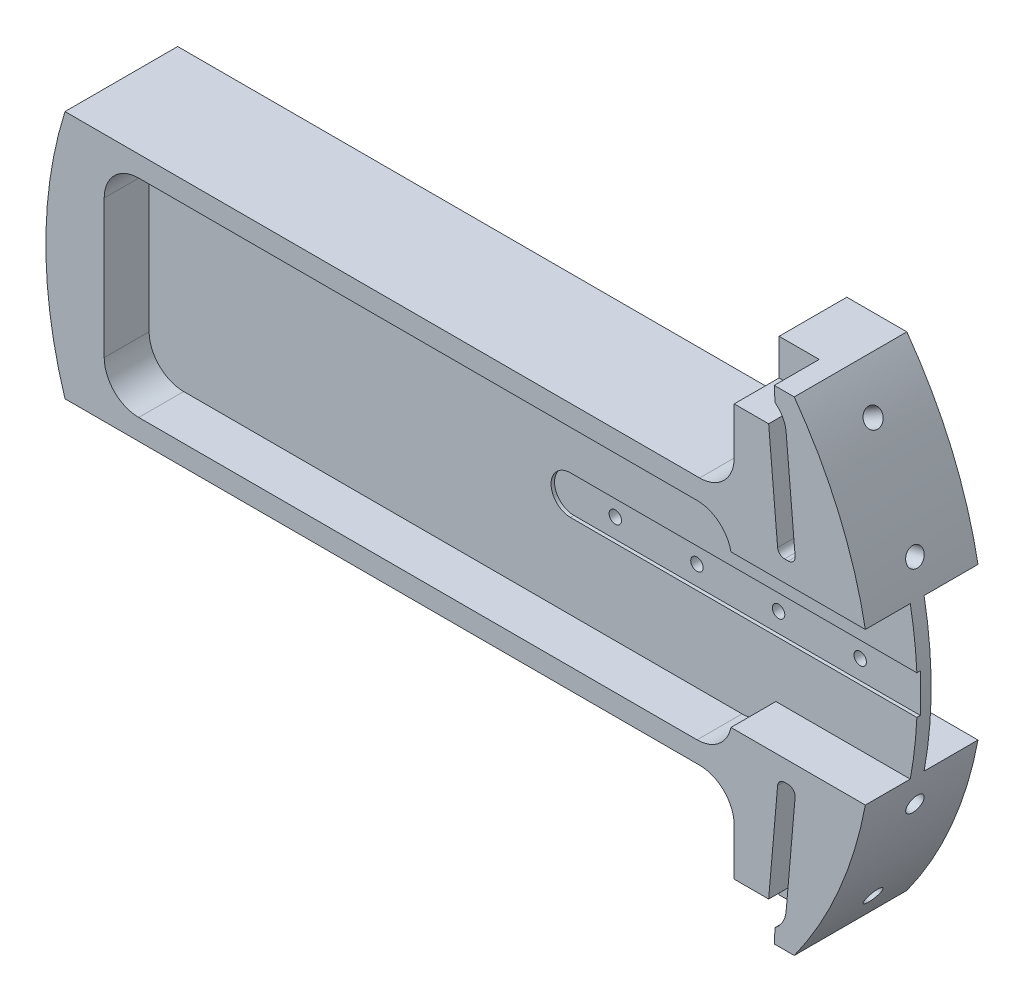
SolidWorks part; units mm, degrees
ref_plane "Front Plane" through (0, 0, 0) normal (0, 0, 1) x (1, 0, 0)
ref_plane "Top Plane" through (0, 0, 0) normal (0, 1, 0) x (1, 0, 0)
ref_plane "Right Plane" through (0, 0, 0) normal (1, 0, 0) x (0, 0, -1)
sketch "Sketch1" plane through (0, 0, 0) normal (0, 0, 1) x (1, 0, 0)
  line L0 (0, 0) -> (91.8237, 0) construction
  line L2 (-71.5726, 25.4) -> (-65.2226, 25.4)
  line L3 (50.546, 44.45) -> (50.546, 22.86)
  line L4 (50.546, -44.45) -> (50.546, -22.86)
  line L5 (44.196, -16.51) -> (-58.8726, -16.51)
  line L6 (50.546, 44.45) -> (61.5792, 44.45)
  line L7 (50.546, -44.45) -> (61.5792, -44.45)
  line L8 (-65.2226, -22.86) -> (-65.2226, -25.4)
  line L9 (44.196, 16.51) -> (-58.8726, 16.51)
  line L10 (-65.2226, 22.86) -> (-65.2226, 25.4)
  line L11 (-71.5726, -25.4) -> (-65.2226, -25.4)
  arc A0 (61.5792, -44.45) -> (61.5792, 44.45) centre (0, 0) ccw
  circle A1 centre (0, 0) radius 75.946 construction
  arc A2 (-71.5726, 25.4) -> (-71.5726, -25.4) centre (0, 0) ccw
  arc A5 (50.546, 22.86) -> (44.196, 16.51) centre (44.196, 22.86) cw
  arc A6 (-58.8726, 16.51) -> (-65.2226, 22.86) centre (-58.8726, 22.86) cw
  arc A7 (50.546, -22.86) -> (44.196, -16.51) centre (44.196, -22.86) ccw
  arc A8 (-58.8726, -16.51) -> (-65.2226, -22.86) centre (-58.8726, -22.86) ccw
  point P6 (75.946, 0)
  point P17 (0, 0)
  point P30 (50.546, -16.51)
  point P33 (-65.2226, -16.51)
  dimension "D1" = 75.946
  dimension "D8" = 151.892
  dimension "D11" = 75.946
  dimension "D13" = 6.35
  dimension "D2" = 27.94
  dimension "D3" = 6.35
  dimension "D4" = 11.0332
  dimension "D5" = 50.8
  dimension "D6" = 88.9
extrude "Boss-Extrude1" add sketch "Sketch1" along normal blind 2.54
sketch "Sketch2" plane through (0, 0, 2.54) normal (0, 0, 1) x (1, 0, 0)
  line L0 (60.2463, 17.78) -> (56.2059, 64.1603) construction
  line L1 (-13.9228, 0) -> (116.9939, 0) construction
  line L2 (35.7924, 17.78) -> (109.7023, 17.78) construction
  line L3 (61.8653, 17.78) -> (60.0951, 38.1)
  line L4 (58.6516, 17.5) -> (56.8815, 37.82)
  line L5 (56.8815, 37.82) -> (50.546, 37.82)
  line L6 (58.0471, 41.7789) -> (57.9008, 44.704)
  line L7 (57.9008, 44.704) -> (61.395, 44.704)
  line L8 (50.546, 37.82) -> (50.546, 16.5667)
  line L9 (50.546, 16.5667) -> (57.3661, 16.5667)
  line L10 (60.7595, 15.0941) -> (60.7595, 13.5449)
  line L11 (60.7595, 13.5449) -> (74.7284, 13.5449)
  line L12 (60.2463, -17.78) -> (56.2059, -64.1603) construction
  line L13 (60.7595, -13.5449) -> (74.7284, -13.5449)
  line L14 (60.7595, -15.0941) -> (60.7595, -13.5449)
  line L15 (50.546, -16.5667) -> (57.3661, -16.5667)
  line L16 (50.546, -37.82) -> (50.546, -16.5667)
  line L17 (57.9008, -44.704) -> (61.395, -44.704)
  line L18 (58.0471, -41.7789) -> (57.9008, -44.704)
  line L19 (56.8815, -37.82) -> (50.546, -37.82)
  line L20 (58.6516, -17.5) -> (56.8815, -37.82)
  line L21 (61.8653, -17.78) -> (60.0951, -38.1)
  line L22 (96.3863, 0) -> (96.3863, 82.276) construction
  arc A0 (61.5792, -44.45) -> (61.5792, 44.45) centre (0, 0) ccw construction
  arc A1 (60.0951, 38.1) -> (58.0471, 41.7789) centre (54.9639, 37.653) ccw
  arc A2 (57.3661, 16.5667) -> (58.6516, 17.5) centre (57.3661, 17.9187) ccw
  arc A3 (61.8653, 17.78) -> (60.7595, 15.0941) centre (58.7167, 17.5057) cw
  arc A4 (74.7284, 13.5449) -> (61.395, 44.704) centre (0, 0) ccw
  arc A5 (74.7284, -13.5449) -> (61.395, -44.704) centre (0, 0) cw
  arc A6 (61.8653, -17.78) -> (60.7595, -15.0941) centre (58.7167, -17.5057) ccw
  arc A7 (57.3661, -16.5667) -> (58.6516, -17.5) centre (57.3661, -17.9187) cw
  arc A8 (60.0951, -38.1) -> (58.0471, -41.7789) centre (54.9639, -37.653) cw
  point P0 (75.946, 0)
  point P1 (60.2463, 17.78)
  point P49 (96.3863, 44.704)
  dimension "D6" = 75.946
  dimension "D1" = 17.78
  dimension "D2" = 15.6997
  dimension "D3" = 85.021
  dimension "D4" = 1.6129
  dimension "D5" = 20.32
  dimension "D7" = 44.704
  dimension "D8" = 44.704
  dimension "D9" = 25.4
extrude "Boss-Extrude2" add sketch "Sketch2" along normal blind 8.255
sketch "Sketch3" plane through (0, 0, 2.54) normal (0, 0, 1) x (1, 0, 0)
  line L0 (-6.3906, 0) -> (92.2963, 0) construction
  line L1 (50.546, 44.45) -> (50.546, 22.86) construction
  line L2 (12.192, -3.55) -> (76.962, -3.55)
  line L3 (12.192, -3.55) -> (12.192, 3.55)
  line L4 (12.192, 3.55) -> (76.962, 3.55)
  line L5 (76.962, -3.55) -> (76.962, 3.55)
  line L6 (12.192, -3.55) -> (76.962, 3.55) construction
  line L7 (12.192, 3.55) -> (76.962, -3.55) construction
  point P3 (44.577, 0)
  dimension "D1" = 7.1
  dimension "D2" = 64.77
  dimension "D3" = 38.354
extrude "Cut-Extrude1" cut sketch "Sketch3" against normal blind 0.635
sketch "Sketch6" plane through (0, 0, 0) normal (0, 0, -1) x (-1, 0, 0)
  line L1 (102.4877, 0) -> (-122.8054, 0) construction
sketch "Sketch7" plane through (0, 0, 0) normal (0, 0, 1) x (1, 0, 0)
  line L0 (0, 0) -> (107.1474, 0) construction
  line L1 (0, 0) -> (65.9911, 38.1) construction
  dimension "D1" = 30
ref_plane "Plane2" through (65.7712, 37.973, 0) normal (0.866, 0.5, 0) x (0, 0, -1)
sketch "Sketch4" plane through (0, 0, 1.905) normal (0, 0, 1) x (1, 0, 0)
  line L0 (12.192, 3.55) -> (12.192, -3.55) construction
  line L1 (-1.4827, 0) -> (103.4049, 0) construction
  circle A0 centre (19.812, 0) radius 1.143
  circle A1 centre (34.812, 0) radius 1.143
  circle A2 centre (49.812, 0) radius 1.143
  circle A3 centre (64.812, 0) radius 1.143
  point P2 (12.192, 0)
  dimension "D2" = 2.286
  dimension "D4" = 15
  dimension "D1" = 7.62
  dimension "D5" = 19.812
  dimension "D3" = 4
extrude "Cut-Extrude2" cut sketch "Sketch4" against normal blind 11.43
sketch "Sketch19" plane through (0, 0, 2.54) normal (0, 0, 1) x (1, 0, 0)
  line L0 (-71.5726, -25.4) -> (-65.2226, -25.4) construction
  line L3 (-71.5726, -25.4) -> (-65.2226, -25.4)
  line L4 (-65.2226, -25.4) -> (-65.2226, 25.4)
  line L5 (-65.2226, 25.4) -> (-71.5726, 25.4) construction
  line L6 (-65.2226, 25.4) -> (-71.5726, 25.4)
  circle A0 centre (0, 0) radius 75.946 construction
  arc A3 (-71.5726, 25.4) -> (-71.5726, -25.4) centre (0, 0) ccw
  point P0 (-65.2226, -25.4)
  point P6 (-71.5726, -25.4)
  dimension "D2" = 151.892
  dimension "D1" = 6.35
extrude "Boss-Extrude5" add sketch "Sketch19" along normal blind 8.255
ref_plane "Plane3" through (0, 0, 10.795) normal (0, 0, 1) x (1, 0, 0)
sketch "Sketch22" plane through (0, 0, 10.795) normal (0, 0, 1) x (1, 0, 0)
  line L1 (-75.946, -44.45) -> (75.946, -44.45) construction
  line L2 (-75.946, -44.45) -> (-75.946, 44.45) construction
  line L3 (-75.946, 44.45) -> (75.946, 44.45) construction
  line L4 (75.946, -44.45) -> (75.946, 44.45) construction
  line L5 (-75.946, -44.45) -> (75.946, 44.45) construction
  line L6 (-75.946, 44.45) -> (75.946, -44.45) construction
  point P0 (0, 0)
  dimension "D1" = 88.9
  dimension "D2" = 151.892
sketch "Sketch25" plane through (0, 0, 0) normal (0, 0, 1) x (1, 0, 0)
  line L0 (0, 0) -> (145.0129, 0) construction
  line L1 (0, 0) -> (140.0717, -37.5321) construction
  line L2 (0, 0) -> (125.5848, -72.5064) construction
  circle A0 centre (0, 0) radius 76.2 construction
  point P9 (0, 0)
  dimension "D1" = 152.4
  dimension "D2" = 3
ref_plane "Plane4" through (0, 0, 6.096) normal (0, 0, 1) x (1, 0, 0)
sketch "Sketch27" plane through (0, 0, 6.096) normal (0, 0, 1) x (1, 0, 0)
  line L0 (-98.5098, 0) -> (76.2, 0) construction
  line L1 (0, 0) -> (143.2275, -38.3777) construction
  line L2 (0, 0) -> (128.4143, -74.14) construction
  line L3 (0, 0) -> (143.2275, 38.3777) construction
  line L4 (0, 0) -> (128.4143, 74.14) construction
  line L5 (-95.1532, 25.4962) -> (73.6035, -19.722) construction
  line L6 (-95.1532, -25.4962) -> (73.6035, 19.722) construction
  circle A0 centre (0, 0) radius 76.2 construction
  point P5 (3.2671, -47.4697)
  point P10 (0, 0)
  point P13 (0, 0)
  point P17 (0, 0)
  point P19 (0, 0)
  dimension "D1" = 3
  dimension "D2" = 3
  dimension "D3" = 2
  dimension "D4" = 2
ref_plane "Plane5" through (65.7712, 37.973, 0) normal (0.866, 0.5, 0) x (0, 0, -1)
ref_plane "Plane6" through (73.3582, 19.6563, 0) normal (0.9659, 0.2588, 0) x (0, 0, -1)
ref_plane "Plane7" through (73.3582, -19.6563, 0) normal (0.9659, -0.2588, 0) x (0, 0, -1)
ref_plane "Plane8" through (65.7712, -37.973, 0) normal (0.866, -0.5, 0) x (0, 0, -1)
ref_plane "Plane9" through (0, 0, 0) normal (0, 1, 0) x (1, 0, 0)
ref_plane "Plane10" through (-73.3582, 19.6563, 0) normal (-0.9659, 0.2588, 0) x (0, 0, 1)
ref_plane "Plane11" through (-75.946, 0, 0) normal (-1, 0, 0) x (0, 0, 1)
ref_plane "Plane12" through (-73.3582, -19.6563, 0) normal (-0.9659, -0.2588, 0) x (0, 0, 1)
sketch "Sketch33" plane through (0, 0, 2.54) normal (0, 0, 1) x (1, 0, 0)
  line L0 (44.196, 16.51) -> (-58.8726, 16.51) construction
  line L1 (12.1373, 16.51) -> (-58.8726, 16.51)
  line L2 (44.196, 15.24) -> (-58.8726, 15.24) construction
  line L3 (12.1373, 13.97) -> (-58.8726, 13.97)
  line L4 (0, 0) -> (-34.589, 0) construction
  line L5 (-65.2226, 22.86) -> (-65.2226, 7.62)
  line L6 (12.1373, 13.97) -> (12.1373, 16.51)
  line L7 (12.1373, -13.97) -> (12.1373, -16.51)
  line L8 (44.196, 16.51) -> (-58.8726, 16.51) construction
  line L9 (44.196, -15.24) -> (-58.8726, -15.24) construction
  line L10 (12.1373, -16.51) -> (-58.8726, -16.51)
  line L11 (12.1373, -13.97) -> (-58.8726, -13.97)
  line L12 (-65.2226, -22.86) -> (-65.2226, -7.62)
  arc A0 (-65.2226, 22.86) -> (-58.8726, 16.51) centre (-58.8726, 22.86) ccw construction
  arc A1 (-65.2226, 22.86) -> (-58.8726, 16.51) centre (-58.8726, 22.86) ccw
  arc A2 (-65.2226, 7.62) -> (-58.8726, 13.97) centre (-58.8726, 7.62) cw
  arc A3 (-66.4926, 22.86) -> (-58.8726, 15.24) centre (-58.8726, 22.86) ccw construction
  arc A4 (-65.2226, -7.62) -> (-58.8726, -13.97) centre (-58.8726, -7.62) ccw
  arc A5 (-65.2226, -22.86) -> (-58.8726, -16.51) centre (-58.8726, -22.86) cw
  dimension "D2" = 71.0099
  dimension "D3" = 2.54
  dimension "D1" = 1.27
extrude "Boss-Extrude6" add sketch "Sketch33" along normal up to surface (8.255 mm away) up to face at (-69.4909, 0, 10.795)
sketch "Sketch38" plane through (0, 0, 10.795) normal (0, 0, 1) x (1, 0, 0)
  line L0 (12.1373, -13.97) -> (60.7595, -13.97)
  line L1 (60.7595, -13.5449) -> (60.7595, -15.0941) construction
  line L2 (12.1373, -16.51) -> (44.196, -16.51)
  line L3 (61.8653, 17.78) -> (58.2982, 17.78)
  line L4 (58.2982, -17.78) -> (50.546, -22.86)
  line L5 (60.7595, -13.97) -> (60.7595, -15.0941)
  line L6 (12.1373, -16.51) -> (12.1373, -13.97)
  line L7 (63.669, 0) -> (92.2088, 0) construction
  line L8 (12.1373, 16.51) -> (12.1373, 13.97)
  line L9 (60.7595, 13.97) -> (60.7595, 15.0941)
  line L10 (58.2982, 17.78) -> (50.546, 22.86)
  line L11 (12.1373, 16.51) -> (44.196, 16.51)
  line L12 (12.1373, 13.97) -> (60.7595, 13.97)
  line L14 (61.8653, -17.78) -> (58.2982, -17.78)
  arc A0 (50.546, -22.86) -> (44.196, -16.51) centre (44.196, -22.86) ccw construction
  arc A1 (50.546, -22.86) -> (44.196, -16.51) centre (44.196, -22.86) ccw
  arc A2 (61.8653, -17.78) -> (60.7595, -15.0941) centre (58.7167, -17.5057) ccw construction
  arc A3 (61.8653, -17.78) -> (60.7595, -15.0941) centre (58.7167, -17.5057) ccw
  circle A4 centre (64.812, 0) radius 1.143 construction
  arc A5 (61.8653, 17.78) -> (60.7595, 15.0941) centre (58.7167, 17.5057) cw
  arc A6 (50.546, 22.86) -> (44.196, 16.51) centre (44.196, 22.86) cw
extrude "Boss-Extrude7" add sketch "Sketch38" against normal up to surface (8.255 mm away) up to face at (39.9553, -0.238, 2.54)
sketch "Sketch39" plane through (0, 0, 10.795) normal (0, 0, 1) x (1, 0, 0)
  line L1 (60.7595, -13.97) -> (74.7348, -13.97)
  line L2 (60.7595, -13.97) -> (60.7595, 13.97)
  line L3 (60.7595, 13.97) -> (74.7348, 13.97)
  line L4 (74.7348, -13.97) -> (74.7348, 13.97)
extrude "Cut-Extrude19" cut sketch "Sketch39" against normal up to surface (8.255 mm away) up to face at (22.2, -0.7139, 2.54)
fillet "Fillet2" radius 1.27 4 edges at (58.6273, -17.78, 6.6675) (61.8653, -17.78, 6.6675) (58.6273, 17.78, 6.6675) (61.8653, 17.78, 6.6675)
sketch "Sketch45" plane through (0, 0, 10.795) normal (0, 0, 1) x (1, 0, 0)
  line L0 (-67.721, -22.7159) -> (54.0765, -22.7159)
  line L1 (54.0765, -22.7159) -> (54.0765, -20.1759)
  line L2 (54.0765, -20.1759) -> (-67.721, -20.1759)
  line L3 (-65.2226, -7.62) -> (-65.2226, 7.62) construction
  line L4 (-67.721, -20.1759) -> (-67.721, -22.7159)
  line L5 (-65.2226, 0) -> (-20.8376, 0) construction
  line L6 (-67.721, 20.1759) -> (-67.721, 22.7159)
  line L7 (54.0765, 20.1759) -> (-67.721, 20.1759)
  line L8 (54.0765, 22.7159) -> (54.0765, 20.1759)
  line L9 (-67.721, 22.7159) -> (54.0765, 22.7159)
  dimension "D1" = 2.54
extrude "Boss-Extrude8" add sketch "Sketch45" against normal up to surface (10.795 mm away) up to face at (65.955, 0, 0)
sketch "Sketch46" plane through (0, 0, 10.795) normal (0, 0, 1) x (1, 0, 0)
  line L0 (-64.6274, 20.1759) -> (49.9508, 20.1759) construction
  line L1 (-65.2226, 20.1759) -> (49.9508, 20.1759)
  line L2 (-65.2226, 20.1759) -> (-65.2226, -20.1759)
  line L3 (-65.2226, -20.1759) -> (49.9508, -20.1759)
  line L4 (49.9508, 20.1759) -> (49.9508, -20.1759)
  line L5 (-65.2226, -7.62) -> (-65.2226, 7.62) construction
extrude "Cut-Extrude20" cut sketch "Sketch46" against normal up to surface (8.255 mm away) up to face at (7.459, -1.042, 2.54)
sketch "Sketch48" plane through (0, 0, 2.54) normal (0, 0, 1) x (1, 0, 0)
  line L0 (12.192, 0) -> (-88.754, 0) construction
  line L1 (-65.2226, 20.1759) -> (49.9508, 20.1759)
  line L2 (-65.2226, 20.1759) -> (-65.2226, 13.97)
  line L3 (-65.2226, 13.97) -> (49.9508, 13.97)
  line L4 (49.9508, 20.1759) -> (49.9508, 13.97)
  line L5 (12.192, 3.55) -> (12.192, -3.55) construction
  line L6 (49.9508, -20.1759) -> (49.9508, -13.97)
  line L7 (-65.2226, -13.97) -> (49.9508, -13.97)
  line L8 (-65.2226, -20.1759) -> (-65.2226, -13.97)
  line L9 (-65.2226, -20.1759) -> (49.9508, -20.1759)
extrude "Boss-Extrude9" add sketch "Sketch48" against normal up to surface (2.54 mm away) up to face at (-7.3383, 17.9236, 0)
sketch "Sketch51" plane through (0, 0, 10.795) normal (0, 0, 1) x (1, 0, 0)
  line L0 (-80.7764, 25.4) -> (-80.7764, 22.7159)
  line L1 (-65.2226, 22.7159) -> (-80.7764, 22.7159)
  line L2 (63.669, 0) -> (102.0102, 0) construction
  line L3 (50.546, -22.7159) -> (-65.2226, -22.7159)
  line L4 (50.546, -22.7159) -> (50.546, -25.4)
  line L5 (50.546, -25.4) -> (-65.2226, -25.4)
  line L6 (-65.2226, 25.4) -> (-80.7764, 25.4)
  line L7 (50.546, 25.4) -> (-65.2226, 25.4)
  line L8 (50.546, 22.7159) -> (50.546, 25.4)
  line L9 (-65.2226, -25.4) -> (-80.7764, -25.4)
  line L10 (50.546, 22.7159) -> (-65.2226, 22.7159)
  line L11 (-65.2226, -22.7159) -> (-80.7764, -22.7159)
  line L12 (-80.7764, -25.4) -> (-80.7764, -22.7159)
  circle A0 centre (64.812, 0) radius 1.143 construction
extrude "Cut-Extrude24" cut sketch "Sketch51" against normal blind 43.688
sketch "Sketch52" plane through (0, 0, 2.54) normal (0, 0, 1) x (1, 0, 0)
  line L0 (12.192, 3.55) -> (12.192, -3.55) construction
  line L1 (12.192, -3.55) -> (12.192, 3.55)
  arc A0 (12.192, 3.55) -> (12.192, -3.55) centre (12.192, 0) ccw
extrude "Cut-Extrude25" cut sketch "Sketch52" against normal up to surface (0.635 mm away) up to face at (65.955, 0, 1.905)
sketch "Sketch53" plane through (0, 0, 0) normal (0, 0, -1) x (-1, 0, 0)
  line L0 (-63.669, 0) -> (-88.114, 0) construction
  line L1 (-50.546, -44.45) -> (-63.8852, -44.45)
  line L2 (-50.546, -44.45) -> (-50.546, -49.2353)
  line L3 (-50.546, -49.2353) -> (-63.8852, -49.2353)
  line L4 (-63.8852, -44.45) -> (-63.8852, -49.2353)
  line L5 (-63.8852, 44.45) -> (-63.8852, 49.2353)
  line L6 (-50.546, 49.2353) -> (-63.8852, 49.2353)
  line L7 (-50.546, 44.45) -> (-50.546, 49.2353)
  line L8 (-50.546, 44.45) -> (-63.8852, 44.45)
  circle A0 centre (-64.812, 0) radius 1.143 construction
extrude "Cut-Extrude26" cut sketch "Sketch53" against normal blind 43.688
sketch "Sketch58" plane through (0, 0, 10.795) normal (0, 0, 1) x (1, 0, 0)
  line L2 (-65.2226, 0) -> (-92.2383, 0) construction
  line L3 (-65.2226, -20.1759) -> (-65.2226, 20.1759) construction
  line L4 (50.546, 37.82) -> (50.546, 22.7159) construction
  line L5 (50.546, 22.86) -> (-72.4239, 22.86)
  line L6 (50.546, 22.86) -> (50.546, 19.05)
  line L7 (50.546, 19.05) -> (-65.2226, 19.05)
  line L8 (-72.4692, 22.7159) -> (-65.2226, 22.7159)
  line L9 (-65.2226, -22.7159) -> (-65.2226, -19.05)
  line L10 (50.546, 22.7159) -> (-72.4692, 22.7159) construction
  line L11 (-65.2226, 22.7159) -> (-65.2226, 19.05)
  line L12 (-72.4692, -22.7159) -> (-65.2226, -22.7159)
  line L13 (50.546, -19.05) -> (-65.2226, -19.05)
  line L14 (50.546, -22.86) -> (50.546, -19.05)
  line L15 (50.546, -22.86) -> (-72.4239, -22.86)
  arc A0 (-72.4239, 22.86) -> (-72.4692, 22.7159) centre (0, 0) ccw
  arc A2 (-72.4239, -22.86) -> (-72.4692, -22.7159) centre (0, 0) cw
  dimension "D1" = 3.81
  dimension "D2" = 22.86
extrude "Boss-Extrude10" add sketch "Sketch58" against normal up to surface (10.795 mm away) up to face at (23.9117, 0, 0)
fillet "Fillet8" radius 6.35 6 edges at (50.546, 22.86, 5.3975) (50.546, -22.86, 5.3975) (49.9508, 19.05, 6.6675) (49.9508, -19.05, 6.6675) (-65.2226, 19.05, 6.6675) (-65.2226, -19.05, 6.6675)
sketch "Sketch59" plane through (0, 0, 10.795) normal (0, 0, 1) x (1, 0, 0)
  line L1 (50.546, -29.21) -> (50.546, -44.45)
  line L2 (50.546, -44.45) -> (61.5792, -44.45)
  line L3 (50.546, 29.21) -> (50.546, 44.45)
  line L4 (50.546, 44.45) -> (61.5792, 44.45)
  line L21 (74.6501, -13.97) -> (49.9508, -13.97)
  line L22 (43.7291, -19.05) -> (-58.8726, -19.05)
  line L23 (-65.2226, -12.7) -> (-65.2226, 12.7)
  line L24 (-58.8726, 19.05) -> (43.7291, 19.05)
  line L25 (49.9508, 13.97) -> (74.6501, 13.97)
  line L26 (61.5792, 44.45) -> (57.9135, 44.45)
  line L27 (57.9135, 44.45) -> (58.0471, 41.7789)
  line L28 (60.0951, 38.1) -> (61.745, 19.1602)
  line L29 (60.4798, 17.78) -> (59.7914, 17.78)
  line L30 (58.5262, 18.9398) -> (56.8815, 37.82)
  line L31 (56.8815, 37.82) -> (50.546, 37.82)
  line L32 (50.546, 37.82) -> (50.546, 29.21)
  line L33 (44.196, 22.86) -> (-72.4239, 22.86)
  line L34 (-72.4239, -22.86) -> (44.196, -22.86)
  line L35 (50.546, -29.21) -> (50.546, -37.82)
  line L36 (50.546, -37.82) -> (56.8815, -37.82)
  line L37 (56.8815, -37.82) -> (58.5262, -18.9398)
  line L38 (59.7914, -17.78) -> (60.4798, -17.78)
  line L39 (61.745, -19.1602) -> (60.0951, -38.1)
  line L40 (58.0471, -41.7789) -> (57.9135, -44.45)
  line L41 (57.9135, -44.45) -> (61.5792, -44.45)
  line L42 (74.6501, -13.97) -> (49.9508, -13.97)
  line L43 (43.7291, -19.05) -> (-58.8726, -19.05)
  line L44 (-65.2226, -12.7) -> (-65.2226, 12.7)
  line L45 (-58.8726, 19.05) -> (43.7291, 19.05)
  line L46 (49.9508, 13.97) -> (74.6501, 13.97)
  line L54 (44.196, 22.86) -> (-72.4239, 22.86)
  line L55 (-72.4239, -22.86) -> (44.196, -22.86)
  arc A15 (43.7291, -19.05) -> (49.9508, -13.97) centre (43.7291, -12.7) ccw
  arc A16 (-65.2226, -12.7) -> (-58.8726, -19.05) centre (-58.8726, -12.7) ccw
  arc A17 (-58.8726, 19.05) -> (-65.2226, 12.7) centre (-58.8726, 12.7) ccw
  arc A18 (49.9508, 13.97) -> (43.7291, 19.05) centre (43.7291, 12.7) ccw
  arc A19 (74.6501, 13.97) -> (61.5792, 44.45) centre (0, 0) ccw
  arc A20 (60.0951, 38.1) -> (58.0471, 41.7789) centre (54.9639, 37.653) ccw
  arc A21 (60.4798, 17.78) -> (61.745, 19.1602) centre (60.4798, 19.05) ccw
  arc A22 (58.5262, 18.9398) -> (59.7914, 17.78) centre (59.7914, 19.05) ccw
  arc A23 (44.196, 22.86) -> (50.546, 29.21) centre (44.196, 29.21) ccw
  arc A24 (-72.4239, 22.86) -> (-72.4239, -22.86) centre (0, 0) ccw
  arc A25 (50.546, -29.21) -> (44.196, -22.86) centre (44.196, -29.21) ccw
  arc A26 (59.7914, -17.78) -> (58.5262, -18.9398) centre (59.7914, -19.05) ccw
  arc A27 (61.745, -19.1602) -> (60.4798, -17.78) centre (60.4798, -19.05) ccw
  arc A28 (58.0471, -41.7789) -> (60.0951, -38.1) centre (54.9639, -37.653) ccw
  arc A29 (61.5792, -44.45) -> (74.6501, -13.97) centre (0, 0) ccw
  arc A30 (43.7291, -19.05) -> (49.9508, -13.97) centre (43.7291, -12.7) ccw
  arc A31 (-65.2226, -12.7) -> (-58.8726, -19.05) centre (-58.8726, -12.7) ccw
  arc A32 (-58.8726, 19.05) -> (-65.2226, 12.7) centre (-58.8726, 12.7) ccw
  arc A33 (49.9508, 13.97) -> (43.7291, 19.05) centre (43.7291, 12.7) ccw
  arc A34 (74.6501, 13.97) -> (61.5792, 44.45) centre (0, 0) ccw
  arc A38 (44.196, 22.86) -> (50.546, 29.21) centre (44.196, 29.21) ccw
  arc A39 (-72.4239, 22.86) -> (-72.4239, -22.86) centre (0, 0) ccw
  arc A40 (50.546, -29.21) -> (44.196, -22.86) centre (44.196, -29.21) ccw
  arc A44 (61.5792, -44.45) -> (74.6501, -13.97) centre (0, 0) ccw
  dimension "D1" = 0
extrude "Boss-Extrude13" add sketch "Sketch59" against normal blind 9.906 from surface starting at face at (28.2362, 0, 0)
sketch "Sketch63" plane through (65.7712, 37.973, 0) normal (0.866, 0.5, 0) x (0, 0, -1)
  line L0 (-10.795, 7.7053) -> (9.906, 7.7053) construction
  circle A0 centre (-0.4445, 0.0853) radius 1.651
  point P7 (-0.4445, 7.7053)
  dimension "D1" = 3.302
  dimension "D3" = 7.62
extrude "Cut-Extrude30" cut sketch "Sketch63" against normal blind 7.62
sketch "Sketch64" plane through (73.3582, 19.6563, 0) normal (0.9659, 0.2588, 0) x (0, 0, -1)
  line L0 (-10.795, -5.8269) -> (-2.54, -5.8269) construction
  line L1 (-10.795, 26.9975) -> (-10.795, -5.8269) construction
  circle A0 centre (-0.381, 0.0151) radius 1.651
  dimension "D1" = 3.302
  dimension "D2" = 5.842
  dimension "D3" = 10.414
extrude "Cut-Extrude31" cut sketch "Sketch64" against normal blind 10.16
mirror "Mirror1" about plane through (0, 0, 0) normal (0, 1, 0) of "Cut-Extrude30", "Cut-Extrude31"
sketch "Sketch65" plane through (-75.946, 0, 0) normal (-1, 0, 0) x (0, 0, 1)
  line L0 (-9.906, 22.86) -> (-9.906, -22.86) construction
  circle A0 centre (0.508, 0) radius 1.651
  dimension "D1" = 3.302
  dimension "D2" = 10.414
extrude "Cut-Extrude32" cut sketch "Sketch65" against normal blind 10.16
sketch "Sketch66" plane through (-73.3582, -19.6563, 0) normal (-0.9659, -0.2588, 0) x (0, 0, 1)
  line L0 (-9.906, -3.3364) -> (10.795, -3.3364) construction
  line L1 (-9.906, 40.8257) -> (-9.906, -3.3364) construction
  circle A0 centre (0.508, -0.0344) radius 1.651
  dimension "D1" = 3.302
  dimension "D2" = 3.302
  dimension "D3" = 10.414
extrude "Cut-Extrude33" cut sketch "Sketch66" against normal blind 8.89
sketch "Sketch67" plane through (-73.3582, 19.6563, 0) normal (-0.9659, 0.2588, 0) x (0, 0, 1)
  line L0 (-9.906, 3.3364) -> (10.795, 3.3364) construction
  line L1 (-9.906, 3.3364) -> (-9.906, -40.8257) construction
  circle A0 centre (0.508, 0) radius 1.651
  dimension "D1" = 3.302
  dimension "D2" = 3.3364
  dimension "D3" = 10.414
extrude "Cut-Extrude34" cut sketch "Sketch67" against normal blind 8.89
equation "\"0.15inin\"=0.2"
equation "\"0.45inin\"=0.35"
equation "\"0.55inin\"=0.45"
equation "\"0.125inin\"=0.325"
